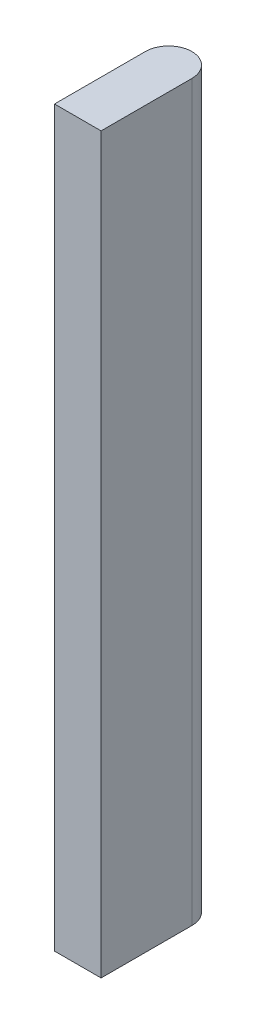
SolidWorks part; units mm, degrees
material "Alliage de zinc AC41A, brut"
ref_plane "Plan de face" through (0, 0, 0) normal (0, 0, 1) x (1, 0, 0)
ref_plane "Plan de dessus" through (0, 0, 0) normal (0, 1, 0) x (1, 0, 0)
ref_plane "Plan de droite" through (0, 0, 0) normal (1, 0, 0) x (0, 0, -1)
sketch "Esquisse1" plane through (0, 0, 0) normal (0, 1, 0) x (1, 0, 0)
  line L0 (0, 2.45) -> (0, -2.45) construction
  line L1 (-1, -2.45) -> (1, -2.45)
  line L2 (-1, -2.45) -> (-1, 1.45)
  line L4 (1, -2.45) -> (1, 1.45)
  arc A0 (1, 1.45) -> (-1, 1.45) centre (0, 1.45) ccw
  point P6 (0, -2.45)
  point P11 (0, 0)
  dimension "D1" = 1
  dimension "D2" = 3.9
extrude "Boss.-Extru.1" add sketch "Esquisse1" along normal blind 31.5
